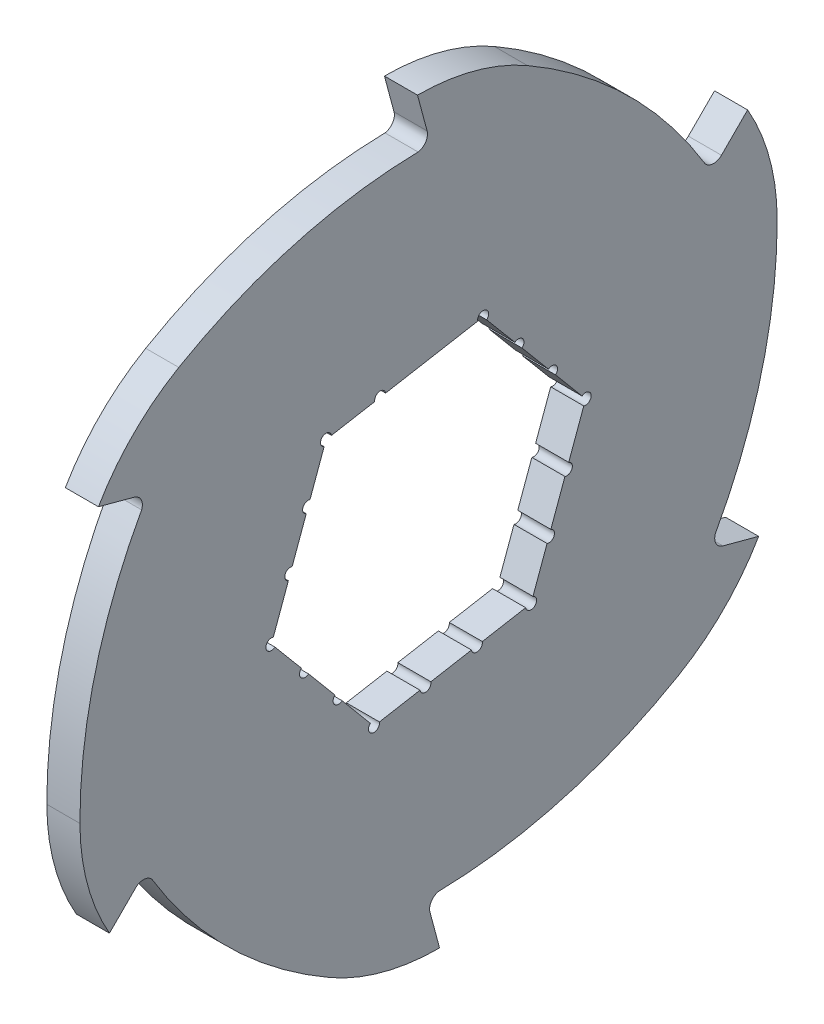
SolidWorks part; units mm, degrees
note: '?' marks a value the reader was unsure of.
material "1.0037 (S235JR)"
ref_plane "Alzado" through (0, 0, 0) normal (0, 0, 1) x (1, 0, 0)
ref_plane "Planta" through (0, 0, 0) normal (0, 1, 0) x (1, 0, 0)
ref_plane "Vista lateral" through (0, 0, 0) normal (1, 0, 0) x (0, 0, -1)
sketch "Sketch1" plane through (0, 0, 0) normal (1, 0, 0) x (0, 0, -1)
  line L0 (-56.6126, 0) -> (65.57, 0) construction
  line L1 (28.4858, 5.0228) -> (9.893, 27.1808)
  line L2 (9.893, 27.1808) -> (-18.5928, 22.158)
  line L3 (-18.5928, 22.158) -> (-28.4858, -5.0228)
  line L4 (-28.4858, -5.0228) -> (-9.893, -27.1808)
  line L5 (-9.893, -27.1808) -> (18.5928, -22.158)
  line L6 (18.5928, -22.158) -> (28.4858, 5.0228)
  circle A0 centre (0, 0) radius 25.05 construction
  circle A1 centre (0, 0) radius 59
  dimension "D2" = 118
  dimension "D1" = 50.1
  dimension "D3" = 50
extrude "Extrude1" add sketch "Sketch1" along normal mid plane 6
ref_axis "Axis1" through (-5.5, 0, 0) along (1, 0, 0)?
sketch "Sketch2" plane through (0, 0, 0) normal (1, 0, 0) x (0, 0, -1)
  line L0 (-2, 67.9618) -> (-0.2627, 61.4781)
  line L1 (0, 0) -> (0, 77.6328) construction
  line L4 (-2.1226, 58.9618) -> (0, 0) construction
  circle A0 centre (0, 0) radius 59 construction
  arc A1 (-2, 67.9618) -> (17.9271, 62.6448) centre (-2, 27.9618) cw
  arc A3 (51.2137, 29.2943) -> (-2.1226, 58.9618) centre (0, 0) ccw
  arc A4 (-0.2627, 61.4781) -> (-2.1226, 58.9618) centre (-2.1946, 60.9605) cw
  arc A5 (17.9271, 62.6448) -> (51.2137, 29.2943) centre (-26.9089, -15.3919) cw
  point P10 (-2, 67.9618)
  dimension "D2" = 40
  dimension "D4" = 2
  dimension "D3" = 9
  dimension "D6" = 90
  dimension "D1" = 15
  dimension "D5" = 2
extrude "Extrude2" add sketch "Sketch2" against normal mid plane 6
fillet "Fillet1" [suppressed] radius 0.6
pattern_circular "CirPattern1" count 6 over 360 about axis through (0, 0, 0) along (1, 0, 0) of "Extrude2", "Fillet1"
sketch "Sketch4" [suppressed] plane through (3, 0, 0) normal (1, 0, 0) x (0, 0, -1)
  circle A0 centre (0, 0) radius 67.9646 construction
  dimension "D1" = 135.9291
hole_wizard "Ø2.0 (2) Diameter Hole1" positions "Sketch5" profile "Sketch7" hole size "Ø2.0" standard "ISO" end condition up to next
sketch "Sketch5" plane through (3, 0, 0) normal (1, 0, 0) x (0, 0, -1)
  point P0 (9.893, 27.1808)
  point P7 (28.4858, 5.0228)
  point P8 (18.5928, -22.158)
  point P9 (-9.893, -27.1808)
  point P10 (-28.4858, -5.0228)
  point P11 (-18.5928, 22.158)
  dimension "D1" = 6
sketch "Sketch7" plane through (3, 27.1808, -9.893) normal (0, 1, 0) x (0, 0, -1)
  line L0 (0, 0) -> (0, 6)
  line L1 (0, 6) -> (1, 6)
  line L2 (1, 6) -> (1, 0)
  line L5 (1, 0) -> (0, 0)
  line L11 (0, -6.35) -> (0, 107.95) construction
  dimension "Diámetro de taladro hasta el siguiente" = 2
  dimension "Profundidad de taladro hasta el siguiente" = 6
hole_wizard "Ø2.0 (2) Diameter Hole3" positions "Sketch10" profile "Sketch11" hole size "Ø2.0" standard "ISO" end condition up to next
sketch "Sketch10" plane through (3, 0, 0) normal (1, 0, 0) x (0, 0, -1)
  line L0 (10.5358, 26.4148) -> (16.3049, 19.5395) construction
  line L1 (27.843, 5.7889) -> (10.5358, 26.4148) construction
  line L2 (16.3049, 19.5395) -> (22.0739, 12.6642) construction
  line L3 (22.0739, 12.6642) -> (27.843, 5.7889) construction
  point P2 (16.3049, 19.5395)
sketch "Sketch11" plane through (3, 19.5395, -16.3049) normal (0, 1, 0) x (0, 0, -1)
  line L0 (0, 0) -> (0, 6.001)
  line L1 (0, 6.001) -> (1, 6.001)
  line L2 (1, 6.001) -> (1, 0)
  line L5 (1, 0) -> (0, 0)
  line L11 (0, -6.35) -> (0, 107.95) construction
  dimension "Diámetro de taladro hasta el siguiente" = 2
  dimension "Profundidad de taladro hasta el siguiente" = 6.001
hole_wizard "Ø2.0 (2) Diameter Hole4" positions "Sketch12" profile "Sketch13" hole size "Ø2.0" standard "ISO" end condition up to next
sketch "Sketch12" plane through (3, 0, 0) normal (1, 0, 0) x (0, 0, -1)
  line L0 (27.843, 5.7889) -> (16.9477, 18.7734) construction
  point P0 (22.3953, 12.2812)
sketch "Sketch13" plane through (3, 12.2812, -22.3953) normal (0, 1, 0) x (0, 0, -1)
  line L0 (0, 0) -> (0, 6.001)
  line L1 (0, 6.001) -> (1, 6.001)
  line L2 (1, 6.001) -> (1, 0)
  line L5 (1, 0) -> (0, 0)
  line L11 (0, -6.35) -> (0, 107.95) construction
  dimension "Diámetro de taladro hasta el siguiente" = 2
  dimension "Profundidad de taladro hasta el siguiente" = 6.001
pattern_circular "CirPattern2" count 6 every 60 about axis through (0, 0, 0) along (1, 0, 0) of "Ø2.0 (2) Diameter Hole3"
pattern_circular "CirPattern3" count 5 every 60 about axis through (0, 0, 0) along (1, 0, 0) of "Ø2.0 (2) Diameter Hole4"
equation "\"D1@Extrude2\"=\"D1@Extrude1\""
